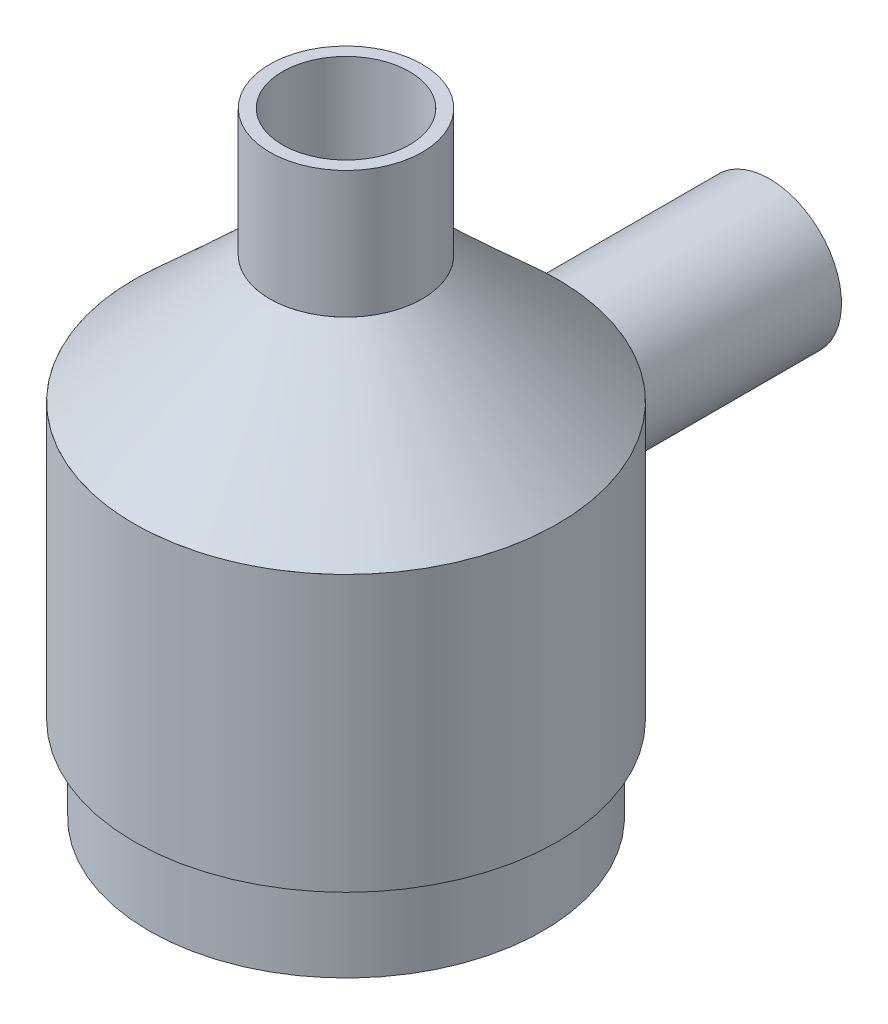
SolidWorks part; units mm, degrees
note: The reader was unsure of these and kept them because the rebuilt part matched: shared geometry of "Sketch6<3>".
material "Alloy Steel"
ref_plane "Front Plane" through (0, 0, 0) normal (0, 0, 1) x (1, 0, 0)
ref_plane "Top Plane" through (0, 0, 0) normal (0, 1, 0) x (1, 0, 0)
ref_plane "Right Plane" through (0, 0, 0) normal (1, 0, 0) x (0, 0, -1)
sketch "Sketch2" plane through (0, 0, 0) normal (0, 1, 0) x (1, 0, 0)
  circle A0 centre (0, 0) radius 25
  dimension "D1" = 50
extrude "Boss-Extrude1" add sketch "Sketch2" along normal blind 32.5
sketch "Sketch3" plane through (0, 0, 0) normal (0, -1, 0) x (1, 0, 0)
  circle A0 centre (0, 0) radius 23.25
  dimension "D1" = 46.5
extrude "Boss-Extrude2" add sketch "Sketch3" along normal blind 10
sketch "Sketch4" plane through (0, -10, 0) normal (0, -1, 0) x (1, 0, 0)
  circle A0 centre (0, 0) radius 22.9
  dimension "D1" = 45.8
extrude "Cut-Extrude1" cut sketch "Sketch4" against normal through all
ref_plane "Plane1" through (0, 47.5, 0) normal (0, 1, 0) x (1, 0, 0)
sketch "Sketch5" plane through (0, 47.5, 0) normal (0, 1, 0) x (1, 0, 0)
  circle A0 centre (0, 0) radius 7.5
  dimension "D1" = 15
extrude "Extrude-Thin1" add sketch "Sketch5" along normal blind 15 separate body thin
surface "Surface-Loft1"
ref_plane "Plane2" through (0, 0, -25) normal (0, 0, -1) x (-1, 0, 0)
sketch "Sketch6" plane through (0, 0, -25) normal (0, 0, -1) x (-1, 0, 0)
  circle A0 centre (0, 21.7869) radius 7.5
  dimension "D1" = 15
extrude "Cut-Extrude2" cut sketch "Sketch6" against normal up to next
extrude "Extrude-Thin4" add sketch "Sketch6<3>" along normal blind 25 and the other way up to surface (25 mm away) thin
sketch "Sketch6<3>" plane through (0, 0, -25) normal (0, 0, -1) x (-1, 0, 0) same geometry as "Sketch6"
